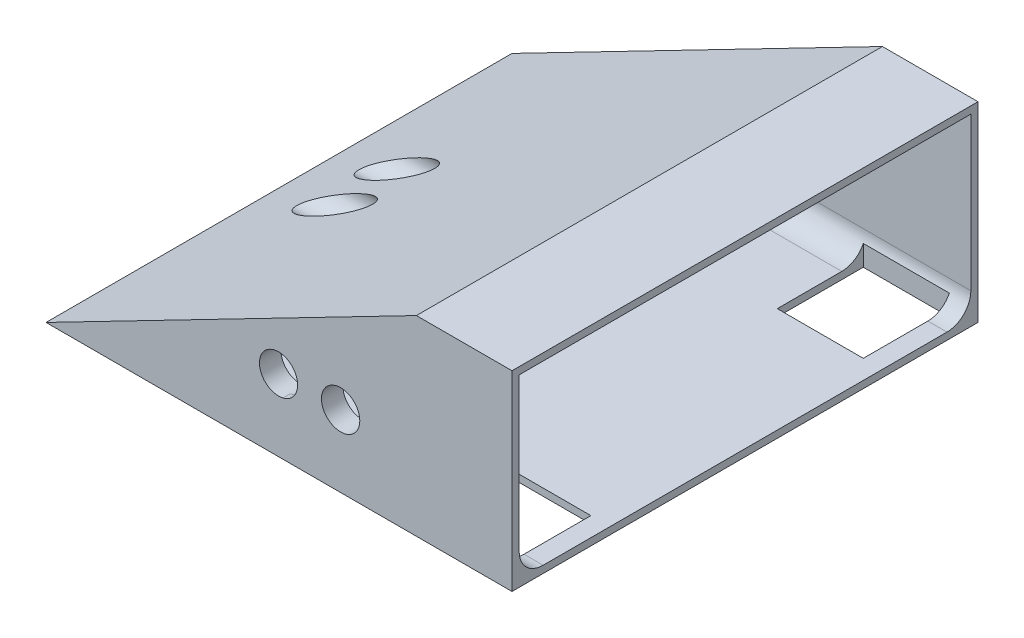
SolidWorks part; units mm, degrees
ref_plane "Front Plane" through (0, 0, 0) normal (0, 0, 1) x (1, 0, 0)
ref_plane "Top Plane" through (0, 0, 0) normal (0, 1, 0) x (1, 0, 0)
ref_plane "Right Plane" through (0, 0, 0) normal (1, 0, 0) x (0, 0, -1)
ref_plane "Plane1" through (0, 0, 0) normal (1, 0, 0) x (0, 0, -1)
ref_plane "Plane2" through (0, 0, 97.5) normal (0, 0, 1) x (1, 0, 0)
ref_plane "Plane3" through (1, 0, 0) normal (1, 0, 0) x (0, 0, -1)
sketch "Sketch2" plane through (0, 0, 0) normal (0, 0, 1) x (1, 0, 0)
  line L0 (0, 0) -> (195, 0)
  line L1 (195, 0) -> (195, 80)
  line L2 (195, 80) -> (155, 80)
  line L3 (155, 80) -> (0, 0)
  dimension "D1" = 195
  dimension "D2" = 40
  dimension "80" = 80
extrude "Robot" add sketch "Sketch2" along normal blind 195
sketch "Sketch3" plane through (0, 0, 195) normal (0, 0, 1) x (1, 0, 0)
  line L0 (0, 0) -> (195, 0) construction
  circle A0 centre (97.2899, 30) radius 8.02
  circle A1 centre (123.2899, 30) radius 8.02
  dimension "D1" = 30
  dimension "D2" = 16.04
  dimension "D4" = 16.04
  dimension "D3" = 26
  dimension "D5" = 30
sketch "Arriba" plane through (0, 80, 0) normal (0, 1, 0) x (1, 0, 0)
  line L0 (195, 0) -> (195, -195) construction
  line L1 (0, 0) -> (0, -195) construction
  line L2 (0, -97.5) -> (195, -97.5) construction
  line L3 (0, 0) -> (195, 0) construction
  line L4 (0, -195) -> (195, -195) construction
  line L5 (97.5, 0) -> (97.5, -195) construction
sketch "Adelante" plane through (0, 0, 0) normal (1, 0, 0) x (0, 0, -1)
  line L0 (0, 80) -> (0, 0) construction
  line L1 (-97.5, 80) -> (-97.5, 0) construction
  line L2 (0, 80) -> (-195, 80) construction
  line L3 (-195, 0) -> (0, 0) construction
  line L4 (-195, 80) -> (-195, 0) construction
  line L5 (0, 0) -> (-195, 0) construction
sketch "Sketch9" plane through (0, 0, 0) normal (0, 0, -1) x (-1, 0, 0)
  line L1 (0, 0) -> (-195, 0) construction
  circle A0 centre (-97.284, 30) radius 8.2
  circle A1 centre (-123.284, 30) radius 8.2
  dimension "D2" = 16.4
  dimension "D4" = 30
  dimension "D6" = 16.4
  dimension "D3" = 30
  dimension "D5" = 26
sketch "Sketch10" plane through (0, 0, 0) normal (0, -1, 0) x (-1, 0, 0)
  line L0 (0, -195) -> (-195, -195) construction
  line L1 (-187, -191) -> (-150, -191)
  line L2 (-187, -191) -> (-187, -154)
  line L3 (-187, -154) -> (-150, -154)
  line L4 (-150, -191) -> (-150, -154)
  line L5 (-195, 0) -> (-195, -195) construction
  dimension "D1" = 4
  dimension "D2" = 8
  dimension "D3" = 37
  dimension "D4" = 37
sketch "Sketch12" plane through (0, 0, 0) normal (0, -1, 0) x (-1, 0, 0)
  line L0 (-195, 0) -> (-195, -195) construction
  line L1 (-187, -40) -> (-151, -40)
  line L2 (-187, -40) -> (-187, -4)
  line L3 (-187, -4) -> (-151, -4)
  line L4 (-151, -40) -> (-151, -4)
  line L5 (0, 0) -> (-195, 0) construction
  dimension "D1" = 8
  dimension "D2" = 4
  dimension "D3" = 36
  dimension "D4" = 36
sketch "Sketch13" plane through (0, 0, 0) normal (0, -1, 0) x (1, 0, 0)
  line L0 (0, 0) -> (195, 0) construction
  line L1 (15, 8) -> (22.1, 8)
  line L2 (15, 8) -> (15, 15.1)
  line L3 (15, 15.1) -> (22.1, 15.1)
  line L4 (22.1, 8) -> (22.1, 15.1)
  line L5 (0, 0) -> (0, 195) construction
  dimension "D1" = 8
  dimension "D2" = 15
  dimension "D3" = 7.1
  dimension "D4" = 7.1
sketch "Sketch14" plane through (0, 0, 0) normal (0, -1, 0) x (-1, 0, 0)
  line L0 (0, -195) -> (-195, -195) construction
  line L1 (-15, -179.9) -> (-22.1, -179.9)
  line L2 (-15, -179.9) -> (-15, -187)
  line L3 (-15, -187) -> (-22.1, -187)
  line L4 (-22.1, -179.9) -> (-22.1, -187)
  line L5 (0, 0) -> (0, -195) construction
  dimension "D1" = 8
  dimension "D2" = 15
  dimension "D3" = 7.1
  dimension "D4" = 7.1
sketch "Sketch15" plane through (0, 0, 0) normal (0, -1, 0) x (-1, 0, 0)
  line L0 (0, -97.5) -> (-195, -97.5) construction
  line L1 (-15, -93.95) -> (-22.1, -93.95)
  line L2 (-15, -93.95) -> (-15, -101.05)
  line L3 (-15, -101.05) -> (-22.1, -101.05)
  line L4 (-22.1, -93.95) -> (-22.1, -101.05)
  line L5 (0, 0) -> (0, -195) construction
  dimension "D1" = 3.55
  dimension "D2" = 3.55
  dimension "D3" = 7.1
  dimension "D4" = 15
shell "Vacio por dentro 3mm" thickness 3 removed face at (195, 40, 97.5)
extrude "Ultrasonico Derecha" cut sketch "Sketch3" against normal blind 3
sketch "Ultrasonico Centro " plane through (0, 0, 0) normal (1, 0, 0) x (0, 0, -1)
  line L0 (0, 0) -> (-195, 0) construction
  line L1 (-97.5, 80) -> (-97.5, 0) construction
  circle A0 centre (-85, 19) radius 8.7
  circle A1 centre (-111, 19) radius 8.7
  dimension "D2" = 17.4
  dimension "D4" = 17.4
  dimension "D1" = 19
  dimension "D3" = 12.5
  dimension "D5" = 13.5
  dimension "D6" = 19
extrude "Ultrasonico Izquierda" cut sketch "Sketch9" against normal blind 3
extrude "Rueda Derecha" cut sketch "Sketch10" against normal blind 3
extrude "Rueda Izquierda" cut sketch "Sketch12" against normal blind 3
extrude "Cyn70 Derecha" cut sketch "Sketch14" against normal blind 4
extrude "Cny70 Centro" cut sketch "Sketch15" against normal blind 4
extrude "Cny70 Izquierda" cut sketch "Sketch13" against normal blind 4
extrude "Cut-Extrude4" cut sketch "Ultrasonico Centro " along normal blind 75
fillet "Fillet2" radius 10 2 edges at (103.6768, 3, 3) (103.6768, 3, 192)
sketch "Sketch16" plane through (0, 0, 195) normal (0, 0, 1) x (1, 0, 0)
  circle A0 centre (123.2899, 30) radius 8.02
  circle A1 centre (123.2899, 30) radius 8.6857
  circle A2 centre (97.3351, 30.0107) radius 8.6857
  circle A3 centre (97.3351, 30.0107) radius 8.02
extrude "Boss-Extrude1" add sketch "Sketch16" against normal blind 9
mirror "Mirror1" about plane through (0, 0, 97.5) normal (0, 0, 1) of "Boss-Extrude1"
sketch "Sketch18" plane through (1, 0, 0) normal (1, 0, 0) x (0, 0, -1)
  circle A0 centre (-85, 19) radius 8.7
  circle A1 centre (-85, 19) radius 8.2
  circle A2 centre (-111, 19) radius 8.7192
  circle A3 centre (-111, 19) radius 8.2
  dimension "D1" = 17.4
  dimension "D2" = 16.4
  dimension "D3" = 16.4
  dimension "D4" = 17.4384
extrude "Boss-Extrude2" add sketch "Sketch18" along normal blind 60
ref_plane "Plane4" through (0, 0, 0) normal (-0.4586, 0.8886, 0) x (0.8886, 0.4586, 0)
sketch "Sketch23" plane through (0, 0, 0) normal (-0.4586, 0.8886, 0) x (0.8886, 0.4586, 0)
  line L1 (0, -64.3188) -> (76.5925, -64.3188)
  line L2 (0, -64.3188) -> (0, -130.2867)
  line L3 (0, -130.2867) -> (76.5925, -130.2867)
  line L4 (76.5925, -64.3188) -> (76.5925, -130.2867)
extrude "Cut-Extrude5" cut sketch "Sketch23" along normal blind 25
